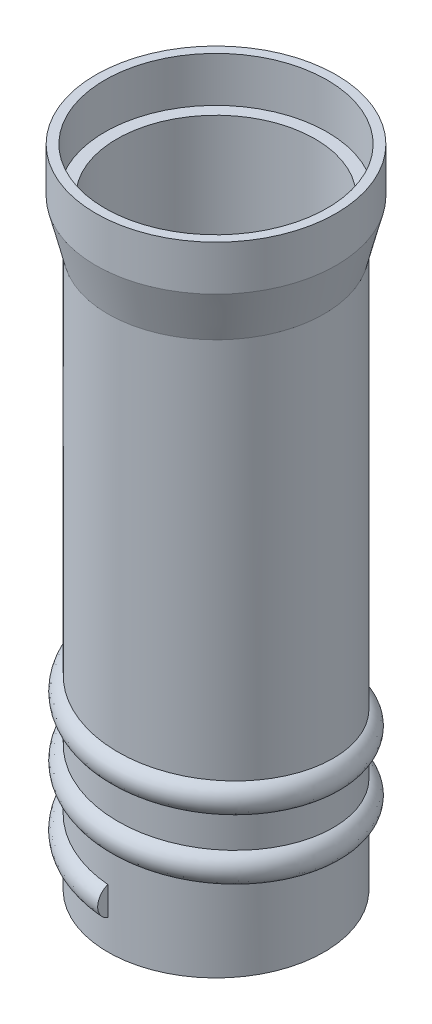
SolidWorks part; units mm, degrees
ref_plane "Front Plane" through (0, 0, 0) normal (0, 0, 1) x (1, 0, 0)
ref_plane "Top Plane" through (0, 0, 0) normal (0, 1, 0) x (1, 0, 0)
ref_plane "Right Plane" through (0, 0, 0) normal (1, 0, 0) x (0, 0, -1)
sketch "Sketch1" plane through (0, 0, 0) normal (0, 1, 0) x (1, 0, 0)
  circle A0 centre (0, 0) radius 18
  circle A1 centre (0, 0) radius 16.5
  dimension "D1" = 36
  dimension "D2" = 33
extrude "Boss-Extrude1" add sketch "Sketch1" along normal blind 95
ref_plane "Plane1" through (0, 95, 0) normal (0, 1, 0) x (1, 0, 0)
sketch "Sketch2" plane through (0, 95, 0) normal (0, 1, 0) x (1, 0, 0)
  circle A0 centre (0, 0) radius 20
  circle A1 centre (0, 0) radius 18.5
  dimension "D1" = 37
  dimension "D2" = 40
extrude "Boss-Extrude2" add sketch "Sketch2" along normal blind 7.5 separate body
sketch "Sketch3" plane through (0, 0, 0) normal (1, 0, 0) x (0, 0, -1)
  line L0 (18, 87) -> (20, 95)
  line L1 (18, 0) -> (18, 95) construction
  line L2 (20, 95) -> (18, 95)
  line L3 (19.8, 95) -> (-19.8, 95) construction
  line L4 (18, 95) -> (18, 87)
  line L5 (0, 102.5) -> (0, 0) construction
  line L6 (18.5, 102.5) -> (-18.5, 102.5) construction
  dimension "D1" = 8
revolve "Revolve1" add sketch "Sketch3" angle 360 about L5
sketch "Sketch4" plane through (0, 0, 0) normal (0, 1, 0) x (1, 0, 0)
  circle A0 centre (0, 0) radius 18
  dimension "D1" = 36
curve "Helix/Spiral1" pitch 10 height 25 radius 18 left hand yes centre (0, 0, 0) axis (0, 1, 0) start towards (0, 0, 1)
sketch "Sketch5" plane through (0, 0, 0) normal (1, 0, 0) x (0, 0, -1)
  line L0 (-18, 87) -> (-18, 0) construction
  line L1 (-18, 4.75) -> (-18, 0)
  arc A0 (-18, 0) -> (-18, 4.75) centre (-17.191, 2.375) cw
  point P3 (-19.7, 2.375)
  dimension "D1" = 1.7
  dimension "D2" = 4.75
sweep "Sweep1" add profiles "Sketch5" path "Helix/Spiral1"
sketch "Sketch6" plane through (0, 0, 0) normal (0, -1, 0) x (1, 0, 0)
  circle A0 centre (0, 0) radius 2.125
  circle A1 centre (0, 0) radius 18
  dimension "D1" = 4.25
  dimension "D2" = 36
extrude "Boss-Extrude3" add sketch "Sketch6" along normal blind 5
